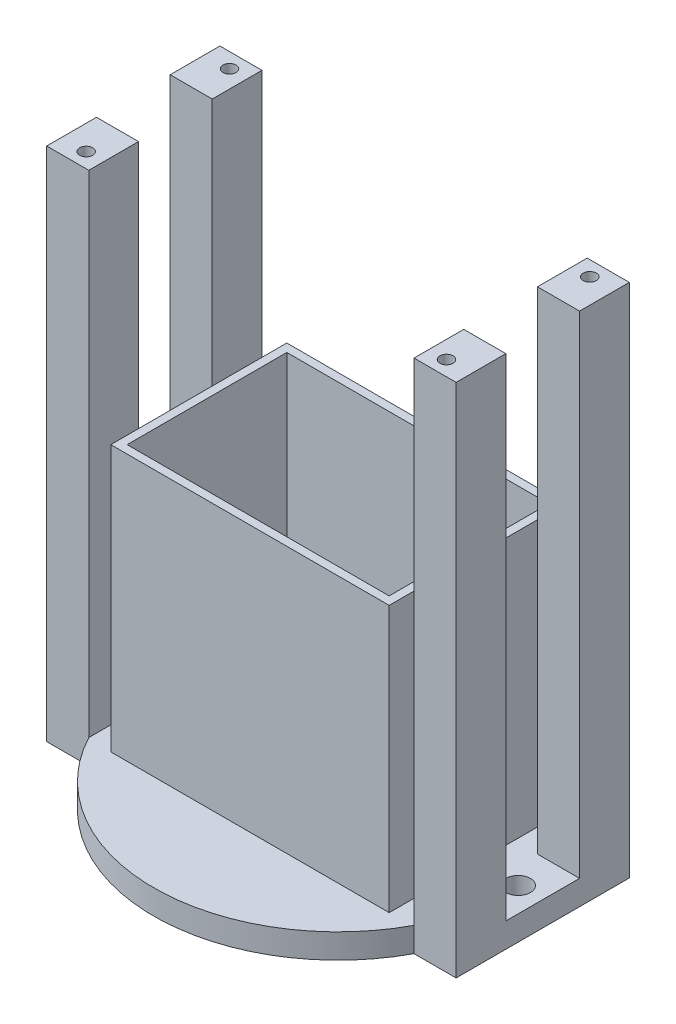
SolidWorks part; units mm, degrees
ref_plane "Front Plane" through (0, 0, 0) normal (0, 0, 1) x (1, 0, 0)
ref_plane "Top Plane" through (0, 0, 0) normal (0, 1, 0) x (1, 0, 0)
ref_plane "Right Plane" through (0, 0, 0) normal (1, 0, 0) x (0, 0, -1)
sketch "Sketch1" plane through (0, 0, 0) normal (0, 1, 0) x (1, 0, 0)
  line L0 (33, 0) -> (-33, 0) construction
  line L2 (-16, 21.15) -> (-50, 21.15)
  line L3 (-16, 21.15) -> (-16, -21.15)
  line L4 (-16, -21.15) -> (-50, -21.15)
  line L5 (-50, 21.15) -> (-50, -21.15)
  line L6 (-16, 21.15) -> (-50, -21.15) construction
  line L7 (-16, -21.15) -> (-50, 21.15) construction
  line L8 (16, 21.15) -> (50, 21.15)
  line L9 (16, 21.15) -> (16, -21.15)
  line L10 (16, -21.15) -> (50, -21.15)
  line L11 (50, 21.15) -> (50, -21.15)
  line L12 (16, 21.15) -> (50, -21.15) construction
  line L13 (16, -21.15) -> (50, 21.15) construction
  circle A0 centre (0, 0) radius 45
  point P6 (0, 0)
  dimension "D1" = 90
  dimension "D2" = 66
  dimension "D3" = 42.3
  dimension "D4" = 42.3
  dimension "D5" = 34
  dimension "D6" = 34
extrude "body" add sketch "Sketch1" along normal blind 6 contours A0 L2 L5 L4 | L2 A0 L4 L3 | L8 A0 L2 L3 L4 L10 L9 | L10 A0 L8 L9 | A0 L10 L11 L8 region at (-29.6863, 0, 0) region at (0, 0, 0) region at (-46.4607, 0, 0) region at (29.6863, 0, 0) region at (46.4607, 0, 0)
sketch "Sketch2" plane through (0, 6, 0) normal (0, 1, 0) x (1, 0, 0)
  line L1 (-50, 21.15) -> (-39.72, 21.15)
  line L2 (-50, 21.15) -> (-50, -21.15)
  line L3 (-50, -21.15) -> (-39.72, -21.15)
  line L4 (-39.72, 21.15) -> (-39.72, -21.15)
  line L5 (50, 21.15) -> (39.72, 21.15)
  line L6 (50, 21.15) -> (50, -21.15)
  line L7 (50, -21.15) -> (39.72, -21.15)
  line L8 (39.72, 21.15) -> (39.72, -21.15)
  line M6 (39.72, -21.15) -> (50, -21.15)
  line M7 (50, -21.15) -> (50, 21.15)
  line M8 (50, 21.15) -> (39.72, 21.15)
extrude "wings" add sketch "Sketch2" along normal blind 120 contours L8 M8 M6 M7 | L2 L1 L4 L3 region at (44.86, 6, 0)
sketch "Sketch3" plane through (0, 126, 0) normal (0, 1, 0) x (1, 0, 0)
  line L0 (44, 0) -> (-44, 0) construction
  line L1 (44, -17.5) -> (44, 17.5) construction
  line L2 (-44, -17.5) -> (-44, 17.5) construction
  circle A0 centre (44, -17.5) radius 1.6
  circle A1 centre (-44, -17.5) radius 1.6
  circle A2 centre (-44, 17.5) radius 1.6
  circle A3 centre (44, 17.5) radius 1.6
  point P4 (0, 0)
  point P8 (44, 0)
  point P11 (-44, 0)
  dimension "D4" = 3.2
  dimension "D5" = 3.2
  dimension "D6" = 3.2
  dimension "D7" = 3.2
  dimension "D1" = 88
  dimension "D2" = 35
  dimension "D3" = 35
extrude "mounting-bore" cut sketch "Sketch3" against normal through all
sketch "Sketch5" plane through (50, 0, 0) normal (1, 0, 0) x (0, 0, -1)
  line L0 (0, 0) -> (0, 6)
  line L1 (21.15, 0) -> (-21.15, 0) construction
  line L2 (9, 6) -> (-9, 6)
  line L3 (9, 6) -> (-9, 6)
  line L4 (9, 6) -> (9, 126)
  line L5 (-9, 6) -> (-9, 126)
  line L6 (9, 126) -> (-9, 126)
  point P7 (0, 6)
  line M9 (21.15, 126) -> (-21.15, 126)
  dimension "D1" = 6
  dimension "D2" = 18
  dimension "D3" = 120
extrude "cut-excess-material" cut sketch "Sketch5" against normal through all contours L5 L2 L4 M9 region at (50, 66, 0)
sketch "Sketch6" plane through (0, 0, 0) normal (0, -1, 0) x (1, 0, 0)
  line L0 (-44, 0) -> (44, 0)
  circle A0 centre (-44, 0) radius 3
  circle A1 centre (44, 0) radius 3
  point P4 (0, 0)
  dimension "D2" = 6
  dimension "D3" = 6
  dimension "D1" = 88
extrude "cut-harness-mount" cut sketch "Sketch6" against normal up to next contours A0 | A1 region at (44, 0, 2.9151) region at (-46.9151, 0, 0)
sketch "Sketch7" plane through (0, 6, 0) normal (0, 1, 0) x (1, 0, 0)
  line L1 (34, -21.5) -> (-34, -21.5)
  line L2 (34, -21.5) -> (34, 21.5)
  line L3 (34, 21.5) -> (-34, 21.5)
  line L4 (-34, -21.5) -> (-34, 21.5)
  line L5 (34, -21.5) -> (-34, 21.5) construction
  line L6 (34, 21.5) -> (-34, -21.5) construction
  line L7 (32, -19.5) -> (-32, -19.5)
  line L8 (32, -19.5) -> (32, 19.5)
  line L9 (32, 19.5) -> (-32, 19.5)
  line L10 (-32, -19.5) -> (-32, 19.5)
  line L11 (32, -19.5) -> (-32, 19.5) construction
  line L12 (32, 19.5) -> (-32, -19.5) construction
  point P0 (0, 0)
  point P6 (0, 0)
  dimension "D1" = 68
  dimension "D2" = 43
  dimension "D3" = 64
  dimension "D4" = 39
extrude "Boss-Extrude3" add sketch "Sketch7" along normal blind 65
equation "\"th\"= 6mm"
equation "\"D1@body\"=\"th\""
equation "\"wing\"= 120mm"
equation "\"D1@wings\"=\"wing\""
equation "\"D1@Sketch5\"=\"th\""
equation "\"D3@Sketch5\"=\"wing\""
